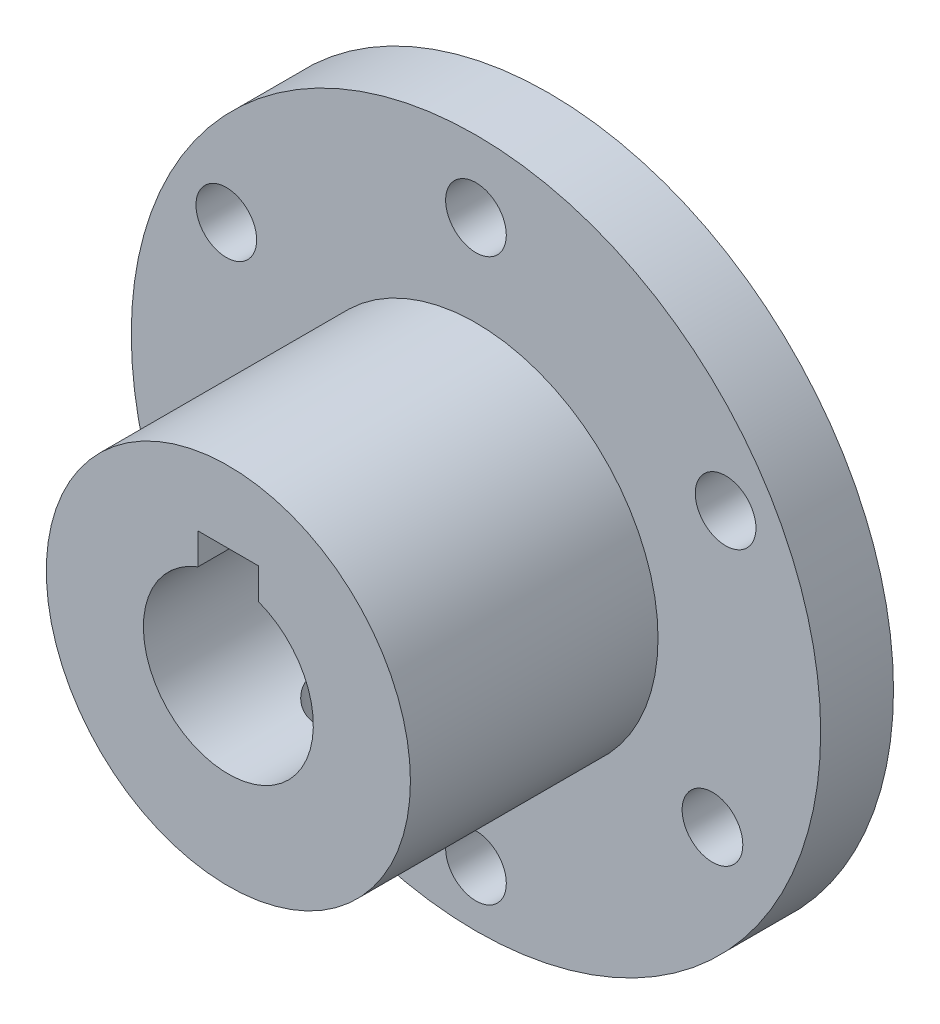
SolidWorks part; units mm, degrees
ref_plane "前视基准面" through (0, 0, 0) normal (0, 0, 1) x (1, 0, 0)
ref_plane "上视基准面" through (0, 0, 0) normal (0, 1, 0) x (1, 0, 0)
ref_plane "右视基准面" through (0, 0, 0) normal (1, 0, 0) x (0, 0, -1)
sketch "草图1" plane through (0, 0, 0) normal (0, 0, 1) x (1, 0, 0)
  circle A0 centre (0, 0) radius 7
  circle A1 centre (0, 0) radius 15
  dimension "D1" = 14
  dimension "D2" = 30
extrude "凸台-拉伸1" add sketch "草图1" along normal blind 20.4
sketch "草图2" plane through (0, 0, 0) normal (0, 0, -1) x (-1, 0, 0)
  circle A0 centre (0, 0) radius 28.4
  circle A1 centre (0, 0) radius 7
  dimension "D1" = 56.8
extrude "凸台-拉伸2" add sketch "草图2" along normal blind 6
sketch "草图3" plane through (0, 0, 0) normal (0, 0, 1) x (1, 0, 0)
  line L0 (0, 0) -> (36.1973, 0) construction
  line L1 (0, 0) -> (39.2724, -22.6739) construction
  circle A0 centre (0, 0) radius 23.75 construction
  circle A1 centre (0, 0) radius 22.5 construction
  circle A2 centre (0, -23.75) radius 2.5
  circle A3 centre (-20.5681, 11.875) radius 2.5
  circle A4 centre (20.5681, 11.875) radius 2.5
  circle A5 centre (19.4856, -11.25) radius 2.5
  circle A6 centre (-19.4856, -11.25) radius 2.5
  circle A7 centre (0, 22.5) radius 2.5
  dimension "D1" = 47.5
  dimension "D2" = 45
  dimension "D3" = 5
  dimension "D6" = 5
  dimension "D5" = 30
  dimension "D4" = 3
  dimension "D7" = 3
extrude "切除-拉伸1" cut sketch "草图3" against normal blind 6
sketch "草图4" plane through (0, 0, 20.4) normal (0, 0, 1) x (1, 0, 0)
  line L1 (2.5, 4.9) -> (-2.5, 4.9)
  line L2 (2.5, 4.9) -> (2.5, 9.1)
  line L3 (2.5, 9.1) -> (-2.5, 9.1)
  line L4 (-2.5, 4.9) -> (-2.5, 9.1)
  line L5 (2.5, 4.9) -> (-2.5, 9.1) construction
  line L6 (2.5, 9.1) -> (-2.5, 4.9) construction
  circle A0 centre (0, 0) radius 7 construction
  point P0 (0, 7)
  dimension "D1" = 5
  dimension "D2" = 4.2
extrude "切除-拉伸2" cut sketch "草图4" against normal blind 50
sketch "草图5" plane through (0, 0, 0) normal (0, 1, 0) x (1, 0, 0)
  line L0 (-15, -20.4) -> (15, -20.4) construction
  circle A0 centre (0, -10.2) radius 3
  dimension "D1" = 6
  dimension "D2" = 10.2
extrude "切除-拉伸3" cut sketch "草图5" against normal blind 20.4
sketch "草图6" plane through (0, 0, -6) normal (0, 0, -1) x (-1, 0, 0)
  circle A0 centre (-20.5681, 11.875) radius 3
sketch "草图7" plane through (0, 0, -6) normal (0, 0, -1) x (-1, 0, 0)
  line L0 (0, 0) -> (19.4856, -11.25)
  line L1 (19.4856, -11.25) -> (24.5951, -14.2)
  circle A0 centre (19.4856, -11.25) radius 3
  circle A1 centre (0, 0) radius 28.4 construction
